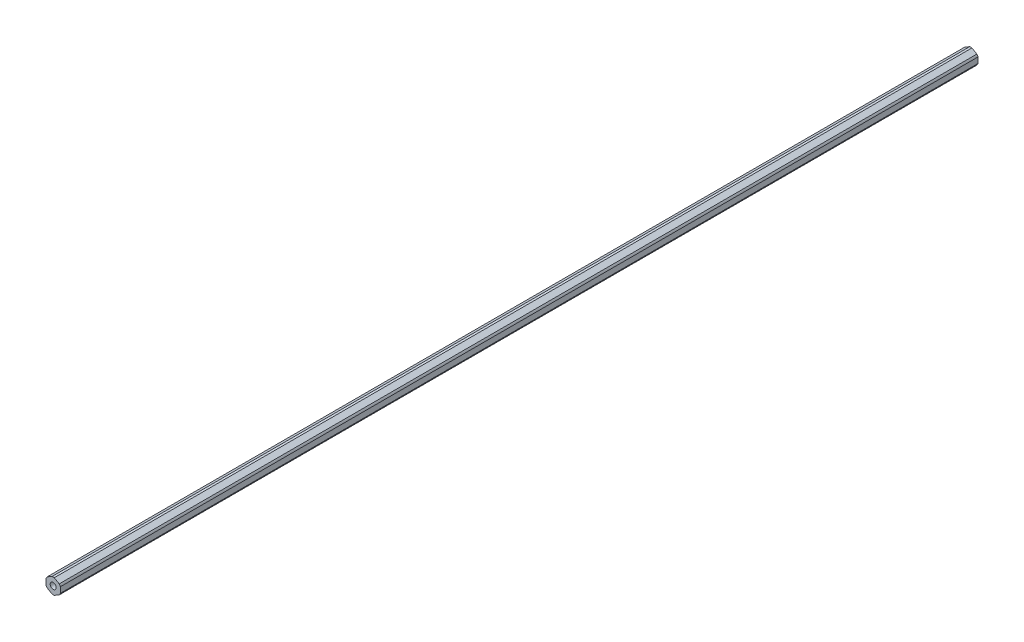
SolidWorks part; units mm, degrees
material "7075-T6 (SN)"
ref_plane "Front Plane" through (0, 0, 0) normal (0, 0, 1) x (1, 0, 0)
ref_plane "Top Plane" through (0, 0, 0) normal (0, 1, 0) x (1, 0, 0)
ref_plane "Right Plane" through (0, 0, 0) normal (1, 0, 0) x (0, 0, -1)
sketch "Sketch2" plane through (0, 0, 0) normal (0, 0, 1) x (1, 0, 0)
  line L1 (0, 5.4993) -> (-4.7625, 2.7496)
  line L2 (-4.7625, 2.7496) -> (-4.7625, -2.7496)
  line L3 (-4.7625, -2.7496) -> (0, -5.4993)
  line L4 (0, -5.4993) -> (4.7625, -2.7496)
  line L5 (4.7625, -2.7496) -> (4.7625, 2.7496)
  line L6 (4.7625, 2.7496) -> (0, 5.4993)
  circle A0 centre (0, 0) radius 4.7625 construction
  circle A2 centre (0, 0) radius 2.0193
  circle A3 centre (0, 0) radius 5.125
  dimension "D1" = 9.525
  dimension "D2" = 10.25
  dimension "D3" = 4.0386
extrude "Boss-Extrude1" add sketch "Sketch2" along normal mid plane 609.6 contours L5 A3 L6 L1 L2 L3 L4 A2 region at (0, 4.9851, 0)
hole_wizard "#10-32 Tapped Hole2" positions "3DSketch1" profile "Sketch6" tap size "#10-32" standard "ANSI Inch"
sketch3d "3DSketch1"
  circle A0 centre (0, 0, 304.8) radius 2.0193 construction
  circle A1 centre (0, 0, -304.8) radius 2.0193 construction
  point P0 (0, 0, -304.8)
  point P2 (0, 0, 304.8)
  point P7 (0, 0, 306.8193)
  point P10 (0, 0, -302.7807)
sketch "Sketch6" plane through (0, 0, -304.8) normal (1, 0, 0) x (0, 1, 0)
  line L0 (0, 0) -> (0, 13.2428)
  line L1 (0, 13.2428) -> (2.0193, 12.0294)
  line L2 (2.0193, 12.0294) -> (2.0193, 0)
  line L5 (2.0193, 0) -> (0, 0)
  line L10 (0, 13.2428) -> (-2.0193, 12.0294) construction
  line L11 (0, -6.35) -> (0, 107.95) construction
  dimension "Tap Drill Dia." = 4.0386
  dimension "Tap Drill Depth" = 12.0294
  dimension "Drill Angle" = 118
cosmetic thread "Hole Thread2"
cosmetic thread "Hole Thread3"
equation "\"D2@Sketch2\"=10.25mm"
